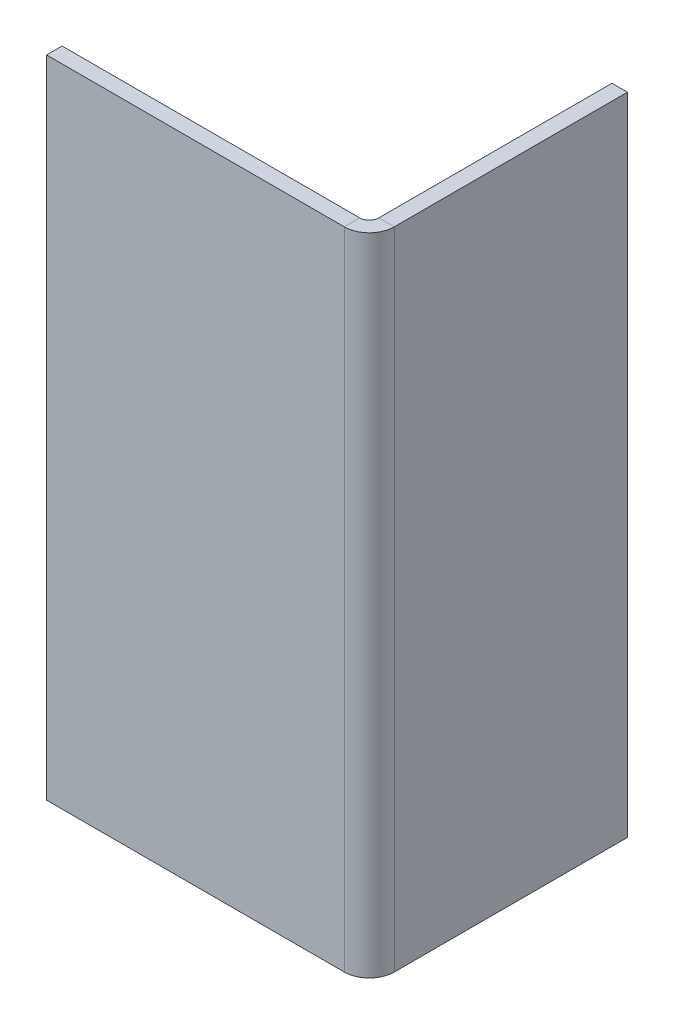
SolidWorks part; units mm, degrees
note: The reader was unsure of these and kept them because the rebuilt part matched: flange length of "Edge-Flange1".
ref_plane "Front Plane" through (0, 0, 0) normal (0, 0, 1) x (1, 0, 0)
ref_plane "Top Plane" through (0, 0, 0) normal (0, 1, 0) x (1, 0, 0)
ref_plane "Right Plane" through (0, 0, 0) normal (1, 0, 0) x (0, 0, -1)
sketch "Sketch4" plane through (0, 0, 0) normal (0, 0, 1) x (1, 0, 0)
  line L1 (0, 0) -> (25, 0)
  line L2 (0, 0) -> (0, 50)
  line L3 (0, 50) -> (25, 50)
  line L4 (25, 0) -> (25, 50)
  dimension "D1" = 50
  dimension "D2" = 25
base flange "Base-Flange1" sketch "Sketch4" thickness 1.2 reverse thickness direction no parameters "D1"=0.7366
edge flange "Edge-Flange1" sketch "Sketch11" flange angle 90 flange length 20 flange position material inside bend radius 0.7366 thickness 1.2 relief rectangular parameters "D6"=10
sketch "Sketch11" plane through (25, 0, -1.2) normal (1, 0, 0) x (0, -1, 0)
  line L0 (0, 0) -> (-50, 0) construction
  line L1 (0, 0) -> (-50, 0)
  line L2 (-50, 0) -> (-50, 18.8)
  line L3 (-50, 18.8) -> (0, 18.8)
  line L4 (0, 18.8) -> (0, 0)
bend "EdgeBend1" bend radius 0.7366 bend angle 90 parameters "D5"=1
sketch "Bend-Lines1" [suppressed] plane through (0, 0, 0) normal (0, 1, 0) x (1, 0, 0)
sketch "Bounding-Box1" [suppressed] plane through (0, 0, 0) normal (0, 1, 0) x (1, 0, 0)
sheet metal parameters "Sheet-Metal1" thickness 1.2 parameters "D1"=0.7366
flat pattern "Flat-Pattern1" [suppressed]
sketch "Bend-Lines2" plane through (0, 0, 0) normal (0, 1, 0) x (1, 0, 0)
sketch3d "Bounding-Box2" [suppressed]
  line L0 (-25, 50, 0) -> (-25, 0, 0) construction
  line L1 (0, 50, 0) -> (0, 0, 0) construction
  line L2 (-25, 50, 0) -> (0, 50, 0) construction
  line L3 (-25, 0, 0) -> (0, 0, 0) construction
sheet metal parameters "Sheet-Metal2" thickness 1.2 parameters "D1"=0.7366
flat pattern "Flat-Pattern1"
sketch "Bend-Lines2" plane through (0, 0, 0) normal (0, 0, 1) x (1, 0, 0)
  line L0 (24.1132, 0) -> (24.1132, 50) construction
  line L1 (24.1132, 0) -> (24.1132, 50) construction
sketch3d "Bounding-Box2" [suppressed]
  line L0 (43.2263, 50, 0) -> (43.2263, 0, 0) construction
  line L1 (0, 50, 0) -> (0, 0, 0) construction
  line L2 (43.2263, 50, 0) -> (0, 50, 0) construction
  line L3 (43.2263, 0, 0) -> (0, 0, 0) construction
bend of the flat pattern "Flatten-<EdgeBend1>1"
